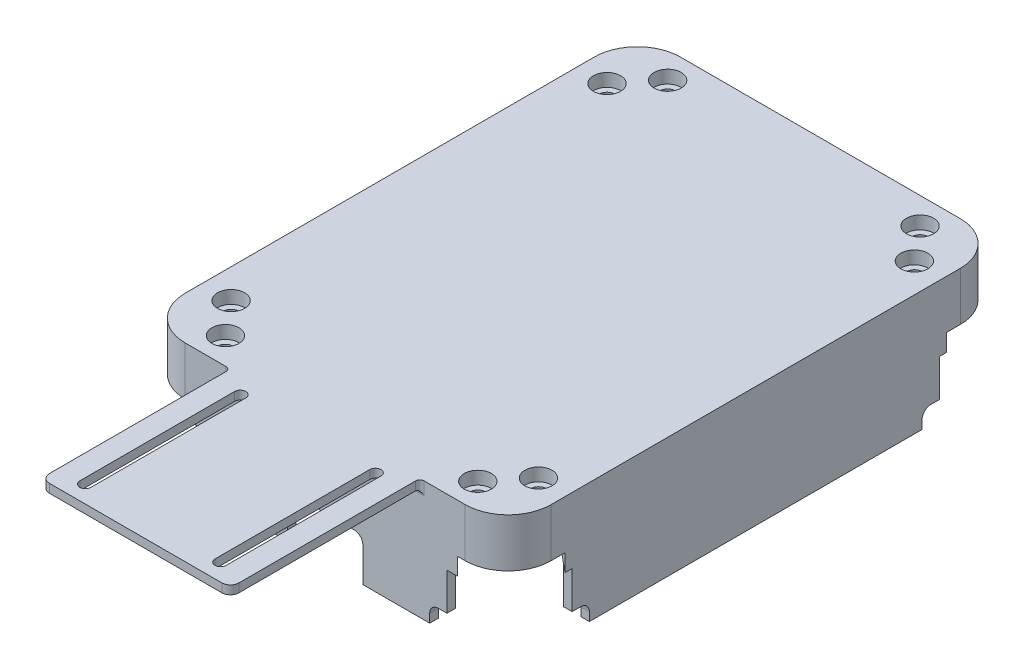
SolidWorks part; units mm, degrees
note: '?' marks a value the reader was unsure of.
material "3-D Printed ABS"
ref_plane "Front Plane" through (0, 0, 0) normal (0, 0, 1) x (1, 0, 0)
ref_plane "Top Plane" through (0, 0, 0) normal (0, 1, 0) x (1, 0, 0)
ref_plane "Right Plane" through (0, 0, 0) normal (1, 0, 0) x (0, 0, -1)
sketch "Sketch1" plane through (0, 0, 0) normal (0, 1, 0) x (1, 0, 0)
  line L1 (-53.975, -73.025) -> (53.975, -73.025)
  line L2 (-53.975, -73.025) -> (-53.975, 73.025)
  line L3 (-53.975, 73.025) -> (53.975, 73.025)
  line L4 (53.975, -73.025) -> (53.975, 73.025)
  line L5 (-53.975, -73.025) -> (53.975, 73.025) construction
  line L6 (-53.975, 73.025) -> (53.975, -73.025) construction
  point P0 (0, 0)
  dimension "D1" = 107.95
  dimension "D2" = 146.05
extrude "Boss-Extrude1" add sketch "Sketch1" against normal blind 2.54
sketch "Sketch13" plane through (0, 0, 0) normal (0, 1, 0) x (1, 0, 0)
  line L0 (0, 155.0212) -> (0, -155.0212) construction
  line L1 (0, 0) -> (-92.0171, 0) construction
  line L2 (53.975, -73.025) -> (53.975, 73.025) construction
  line L3 (53.975, -73.025) -> (28.575, -73.025)
  line L4 (53.975, -73.025) -> (53.975, -47.625)
  line L5 (53.975, -47.625) -> (28.575, -47.625)
  line L6 (28.575, -73.025) -> (28.575, -47.625)
  line L7 (-53.975, -73.025) -> (53.975, -73.025) construction
  line L8 (-28.575, -73.025) -> (-28.575, -47.625)
  line L9 (-53.975, -47.625) -> (-28.575, -47.625)
  line L10 (-53.975, -73.025) -> (-53.975, -47.625)
  line L11 (-53.975, -73.025) -> (-28.575, -73.025)
  line L12 (-53.975, 73.025) -> (-28.575, 73.025)
  line L13 (-53.975, 73.025) -> (-53.975, 47.625)
  line L14 (-53.975, 47.625) -> (-28.575, 47.625)
  line L15 (-28.575, 73.025) -> (-28.575, 47.625)
  line L16 (28.575, 73.025) -> (28.575, 47.625)
  line L17 (53.975, 47.625) -> (28.575, 47.625)
  line L18 (53.975, 73.025) -> (53.975, 47.625)
  line L19 (53.975, 73.025) -> (28.575, 73.025)
  dimension "D1" = 25.4
  dimension "D2" = 25.4
extrude "Boss-Extrude4" add sketch "Sketch13" against normal blind 19.431
sketch "Sketch2" plane through (0, 0, 0) normal (0, 1, 0) x (1, 0, 0)
  line L0 (0, 0) -> (100.1618, 0) construction
  line L1 (0, 0) -> (0, 86.3534) construction
  line L2 (53.975, 73.025) -> (-53.975, 73.025) construction
  line L3 (-53.975, 73.025) -> (-53.975, -73.025) construction
  line L4 (0, 0) -> (-53.975, 73.025) construction
  line L5 (0, 0) -> (-152.4, 0) construction
  line L6 (-152.4, 0) -> (-152.4, 152.4) construction
  line L7 (-152.4, 152.4) -> (0, 152.4) construction
  line L8 (0, 152.4) -> (0, 86.3534) construction
  line L9 (-152.4, 152.4) -> (0, 0) construction
  line L10 (-152.4, 152.4) -> (-41.275, 60.325) construction
  line L11 (-41.275, 60.325) -> (0, 26.1257) construction
  line L13 (-53.975, 44.9974) -> (-30.7521, 73.025) construction
  circle A0 centre (45.3264, 55.4354) radius 3.302
  circle A1 centre (37.2236, 65.2146) radius 3.302
  circle A2 centre (45.3264, -55.4354) radius 3.302
  circle A3 centre (37.2236, -65.2146) radius 3.302
  circle A4 centre (-37.2236, 65.2146) radius 3.302
  circle A5 centre (-45.3264, 55.4354) radius 3.302
  circle A6 centre (-45.3264, -55.4354) radius 3.302
  circle A7 centre (-37.2236, -65.2146) radius 3.302
  point P15 (-41.275, 60.325)
  dimension "D1" = 6.35
  dimension "D3" = 12.7
  dimension "D4" = 6.604
  dimension "D5" = 6.604
  dimension "D2" = 12.7
  dimension "D6" = 6.35
extrude "Cut-Extrude1" cut sketch "Sketch2" against normal through all
sketch "Sketch3" plane through (0, 0, 0) normal (0, 1, 0) x (1, 0, 0)
  line L0 (-53.975, 25.4) -> (53.975, 25.4) construction
  line L1 (-23.495, 60.325) -> (-19.05, 60.325)
  line L2 (-23.495, 60.325) -> (-23.495, 44.45)
  line L3 (-23.495, 44.45) -> (-19.05, 44.45)
  line L4 (-19.05, 60.325) -> (-19.05, 44.45)
  line L5 (19.05, 60.325) -> (19.05, 44.45)
  line L6 (23.495, 44.45) -> (19.05, 44.45)
  line L7 (23.495, 60.325) -> (23.495, 44.45)
  line L8 (23.495, 60.325) -> (19.05, 60.325)
  line L9 (-53.975, 73.025) -> (-53.975, -73.025) construction
  line L10 (53.975, -73.025) -> (53.975, 73.025) construction
  line L11 (0, 0) -> (0, 97.7255) construction
  line L12 (0, 50.8) -> (0, -46.9255) construction
  line L13 (23.495, -9.525) -> (19.05, -9.525)
  line L14 (23.495, -9.525) -> (23.495, 6.35)
  line L15 (23.495, 6.35) -> (19.05, 6.35)
  line L16 (19.05, -9.525) -> (19.05, 6.35)
  line L17 (-19.05, -9.525) -> (-19.05, 6.35)
  line L18 (-23.495, 6.35) -> (-19.05, 6.35)
  line L19 (-23.495, -9.525) -> (-23.495, 6.35)
  line L20 (-23.495, -9.525) -> (-19.05, -9.525)
  dimension "D1" = 15.875
  dimension "D2" = 4.445
  dimension "D3" = 19.05
  dimension "D4" = 25.4
  dimension "D5" = 44.45
extrude "Cut-Extrude2" [suppressed] cut sketch "Sketch3" against normal through all
fillet "Fillet1" radius 12.7 4 edges at (53.975, -9.7155, -73.025) (53.975, -9.7155, 73.025) (-53.975, -9.7155, 73.025) (-53.975, -9.7155, -73.025)
sketch "Sketch4" plane through (0, 0, 0) normal (0, 1, 0) x (1, 0, 0)
  line L0 (0, 0) -> (80.9727, -80.9727) construction
  line L1 (0, 0) -> (-80.9727, -80.9727) construction
  line L2 (69.1118, -51.1513) -> (28.7006, -10.7401)
  line L3 (28.7006, -10.7401) -> (10.7401, -28.7006)
  line L4 (10.7401, -28.7006) -> (51.1513, -69.1118)
  line L5 (51.1513, -69.1118) -> (69.1118, -51.1513)
  line L6 (0, 0) -> (0, -118.7381) construction
  line L7 (0, 0) -> (-98.4177, 0) construction
  line L8 (-51.1513, -69.1118) -> (-69.1118, -51.1513)
  line L9 (-69.1118, -51.1513) -> (-28.7006, -10.7401)
  line L10 (-28.7006, -10.7401) -> (-10.7401, -28.7006)
  line L11 (-10.7401, -28.7006) -> (-51.1513, -69.1118)
  line L12 (-69.1118, 51.1513) -> (-28.7006, 10.7401)
  line L13 (-51.1513, 69.1118) -> (-69.1118, 51.1513)
  line L14 (-10.7401, 28.7006) -> (-51.1513, 69.1118)
  line L15 (-28.7006, 10.7401) -> (-10.7401, 28.7006)
  line L16 (51.1513, 69.1118) -> (69.1118, 51.1513)
  line L17 (69.1118, 51.1513) -> (28.7006, 10.7401)
  line L18 (28.7006, 10.7401) -> (10.7401, 28.7006)
  line L19 (10.7401, 28.7006) -> (51.1513, 69.1118)
  point P6 (19.7204, -19.7204)
  dimension "D1" = 25.4
  dimension "D2" = 57.15
  dimension "D3" = 45
extrude "Cut-Extrude3" [suppressed] cut sketch "Sketch4" against normal blind 1.5875
sketch "Sketch6" [suppressed] plane through (0, 0, 0) normal (0, 1, 0) x (1, 0, 0)
  line L0 (46.3377, -44.1074) -> (34.6634, -32.4331) construction
  line L1 (0, 0) -> (0, -117.7376) construction
  line L2 (0, 0) -> (-151.7285, 0) construction
  line L4 (28.1601, -10.1996) -> (10.1996, -28.1601) construction
  line L5 (50.6107, -68.5712) -> (68.5712, -50.6107) construction
  text T0 "ESC" font "Century Gothic" height in points 22
  dimension "D1" = 45
  dimension "D2" = 20.32
  dimension "D3" = 20.32
extrude "Cut-Extrude5" [suppressed] cut sketch "Sketch6" against normal blind 3.175
sketch "Sketch5" plane through (0, 0, 0) normal (0, 1, 0) x (1, 0, 0)
  line L0 (41.275, 73.025) -> (-41.275, 73.025) construction
  line L1 (14.2875, 15.875) -> (-14.2875, 15.875)
  line L2 (14.2875, 15.875) -> (14.2875, 66.675)
  line L3 (14.2875, 66.675) -> (-14.2875, 66.675)
  line L4 (-14.2875, 15.875) -> (-14.2875, 66.675)
  point P4 (0, 15.875)
  dimension "D1" = 50.8
  dimension "D2" = 28.575
  dimension "D3" = 6.35
extrude "Cut-Extrude4" [suppressed] cut sketch "Sketch5" against normal blind 1.5875
ref_axis "Axis1" through (0, 0.3175, 0) along (0, -1, 0)?
pattern_circular "CirPattern1" [suppressed] count 4 over 360 about axis through (0, 0.3175, 0) along (0, -1, 0)
sketch "Sketch7" plane through (0, 0, 0) normal (0, 1, 0) x (1, 0, 0)
  line L0 (0, 0) -> (0, -54.962) construction
  line L1 (63.4018, -13.3522) -> (38.0018, -13.3522)
  line L2 (63.4018, -13.3522) -> (63.4018, 43.7978)
  line L3 (63.4018, 43.7978) -> (38.0018, 43.7978)
  line L4 (38.0018, -13.3522) -> (38.0018, 43.7978)
  line L5 (-38.0018, -13.3522) -> (-38.0018, 43.7978)
  line L6 (-63.4018, 43.7978) -> (-38.0018, 43.7978)
  line L7 (-63.4018, -13.3522) -> (-63.4018, 43.7978)
  line L8 (-63.4018, -13.3522) -> (-38.0018, -13.3522)
  line L9 (-41.275, -73.025) -> (41.275, -73.025) construction
  line L10 (38.5677, -40.64) -> (-18.5823, -40.64)
  line L11 (38.5677, -40.64) -> (38.5677, -66.04)
  line L12 (38.5677, -66.04) -> (-18.5823, -66.04)
  line L13 (-18.5823, -40.64) -> (-18.5823, -66.04)
  line L14 (38.5677, -40.64) -> (-18.5823, -66.04) construction
  line L15 (38.5677, -66.04) -> (-18.5823, -40.64) construction
  line L16 (19.844, -36.1003) -> (-37.306, -36.1003)
  line L17 (19.844, -36.1003) -> (19.844, -61.5003)
  line L18 (19.844, -61.5003) -> (-37.306, -61.5003)
  line L19 (-37.306, -36.1003) -> (-37.306, -61.5003)
  line L20 (19.844, -36.1003) -> (-37.306, -61.5003) construction
  line L21 (19.844, -61.5003) -> (-37.306, -36.1003) construction
  point P11 (9.9927, -53.34)
  point P18 (-8.731, -48.8003)
  dimension "D1" = 57.15
  dimension "D2" = 25.4
  dimension "D3" = 57.15
  dimension "D4" = 25.4
  dimension "D5" = 6.985
  dimension "D6" = 57.15
  dimension "D7" = 25.4
extrude "Cut-Extrude6" [suppressed] cut sketch "Sketch7" against normal blind 1.27
sketch "Sketch8" plane through (0, 0, 0) normal (0, 1, 0) x (1, 0, 0)
  line L7 (19.05, -31.75) -> (-19.05, -31.75)
  line L8 (19.05, -31.75) -> (19.05, 31.75)
  line L9 (19.05, 31.75) -> (-19.05, 31.75)
  line L10 (-19.05, -31.75) -> (-19.05, 31.75)
  point P0 (0, 0)
  dimension "D1" = 38.1
  dimension "D2" = 31.75
  dimension "D3" = 63.5
extrude "Boss-Extrude3" [suppressed] add sketch "Sketch8" along normal blind 2.54
sketch "Sketch11" plane through (0, 0, 0) normal (0, 1, 0) x (1, 0, 0)
  line L1 (19.05, -9.525) -> (-19.05, -9.525)
  line L2 (19.05, -9.525) -> (19.05, 6.35)
  line L3 (19.05, 6.35) -> (-19.05, 6.35)
  line L4 (-19.05, -9.525) -> (-19.05, 6.35)
extrude "Cut-Extrude9" [suppressed] cut sketch "Sketch11" against normal mid plane 2.54
sketch "Sketch12" [suppressed] plane through (0, 0, 0) normal (0, 1, 0) x (1, 0, 0)
  line L0 (-23.495, -9.525) -> (-19.05, -9.525) construction
  line L1 (12.7, -9.525) -> (-12.7, -9.525)
  line L2 (12.7, -9.525) -> (12.7, 6.35)
  line L3 (12.7, 6.35) -> (-12.7, 6.35)
  line L4 (-12.7, -9.525) -> (-12.7, 6.35)
  line L5 (-19.05, 6.35) -> (-23.495, 6.35) construction
  line L6 (19.05, 52.3875) -> (-19.05, 52.3875) construction
  line L7 (19.05, 60.325) -> (19.05, 44.45) construction
  line L8 (-19.05, 44.45) -> (-19.05, 60.325) construction
  line L9 (-12.7, 114.3) -> (-12.7, 98.425)
  line L10 (12.7, 98.425) -> (-12.7, 98.425)
  line L11 (12.7, 114.3) -> (12.7, 98.425)
  line L12 (12.7, 114.3) -> (-12.7, 114.3)
  point P8 (0, -9.525)
  dimension "D1" = 25.4
extrude "Cut-Extrude12" [suppressed] cut sketch "Sketch12" along normal through all
sketch "Sketch9" plane through (0, 0, 0) normal (0, 1, 0) x (1, 0, 0)
  line L1 (25.1579, -52.4084) -> (-25.6421, -52.4084)
  line L2 (25.1579, -52.4084) -> (25.1579, -1.6084)
  line L3 (25.1579, -1.6084) -> (-25.6421, -1.6084)
  line L4 (-25.6421, -52.4084) -> (-25.6421, -1.6084)
  line L5 (25.1579, -52.4084) -> (-25.6421, -1.6084) construction
  line L6 (25.1579, -1.6084) -> (-25.6421, -52.4084) construction
  point P0 (-0.2421, -27.0084)
  dimension "D1" = 50.8
  dimension "D2" = 50.8
fillet "Fillet2" [suppressed] radius 12.7
sketch "Sketch14" plane through (0, -19.431, 0) normal (0, -1, 0) x (1, 0, 0)
  line L0 (0, 0) -> (0, -152.4) construction
  line L1 (0, 0) -> (152.4, 0) construction
  line L2 (0, 0) -> (152.4, -152.4) construction
  line L3 (152.4, -152.4) -> (41.275, -60.325) construction
  line L4 (41.275, -60.325) -> (27.042, -48.5319) construction
  line L5 (27.042, -48.5319) -> (0, -26.1257) construction
  line L6 (20.692, -28.6742) -> (6.35, -45.9835)
  line L7 (6.35, -45.9835) -> (139.0382, -155.9252)
  line L8 (139.0382, -155.9252) -> (153.3802, -138.6158)
  line L9 (153.3802, -138.6158) -> (20.692, -28.6742)
  line L10 (-20.692, -28.6742) -> (-6.35, -45.9835)
  line L11 (-153.3802, -138.6158) -> (-20.692, -28.6742)
  line L12 (-6.35, -45.9835) -> (-139.0382, -155.9252)
  line L13 (-139.0382, -155.9252) -> (-153.3802, -138.6158)
  line L14 (-153.3802, 138.6158) -> (-20.692, 28.6742)
  line L15 (-139.0382, 155.9252) -> (-153.3802, 138.6158)
  line L16 (-6.35, 45.9835) -> (-139.0382, 155.9252)
  line L17 (-20.692, 28.6742) -> (-6.35, 45.9835)
  line L18 (20.692, 28.6742) -> (6.35, 45.9835)
  line L19 (139.0382, 155.9252) -> (153.3802, 138.6158)
  line L20 (153.3802, 138.6158) -> (20.692, 28.6742)
  line L21 (6.35, 45.9835) -> (139.0382, 155.9252)
  line L22 (41.275, -73.025) -> (-41.275, -73.025) construction
  line L23 (53.975, 60.325) -> (53.975, -60.325) construction
  point P3 (13.521, -37.3288)
  point P6 (41.275, -60.325)
  dimension "D1" = 152.4
  dimension "D2" = 152.4
  dimension "D3" = 6.35
  dimension "D4" = 11.2395
  dimension "D5" = 12.7
  dimension "D6" = 12.7
extrude "Cut-Extrude13" cut sketch "Sketch14" against normal blind 5.08
sketch "Sketch15" plane through (0, 0, 0) normal (0, 1, 0) x (1, 0, 0)
  line L0 (0, 0) -> (72.5178, 0) construction
  line L1 (0, 0) -> (0, 124.598) construction
  circle A0 centre (-45.3264, 55.4354) radius 5.08
  circle A1 centre (45.3264, 55.4354) radius 5.08
  circle A2 centre (37.2236, 65.2146) radius 5.08
  circle A3 centre (45.3264, -55.4354) radius 5.08
  circle A4 centre (37.2236, -65.2146) radius 5.08
  circle A5 centre (-37.2236, -65.2146) radius 5.08
  circle A6 centre (-37.2236, 65.2146) radius 5.08
  circle A7 centre (-45.3264, -55.4354) radius 5.08
extrude "Boss-Extrude5" add sketch "Sketch15" against normal offset from surface (11.811 mm away) 2.54 up to face at (-41.6508, -14.351, -60.7008)
hole_wizard "M4 Clearance Hole1" [suppressed] positions "Sketch18" profile "Sketch16" hole size "M4" standard "ANSI Metric"
sketch "Sketch18" plane through (0, -19.05, 0) normal (0, -1, 0) x (-1, 0, 0)
  point P0 (41.275, 60.325)
  point P3 (41.275, -60.325)
  point P6 (-41.275, -60.325)
  point P9 (-41.275, 60.325)
sketch "Sketch16" plane through (-41.275, -19.05, -60.325) normal (1, 0, 0) x (0, 0, -1)
  line L0 (0, 0) -> (0, 19.05)
  line L1 (0, 19.05) -> (2.25, 19.05)
  line L2 (2.25, 19.05) -> (2.25, 0)
  line L5 (2.25, 0) -> (0, 0)
  line L11 (0, -6.35) -> (0, 107.95) construction
  dimension "Thru Hole Dia." = 4.5
  dimension "Thru Hole Depth" = 19.05
hole_wizard "CBORE for M4 SHCS1" [suppressed] positions "Sketch21" profile "Sketch20" counterbore size "M4" standard "ANSI Metric"
sketch "Sketch21" [suppressed] plane through (0, 0, 0) normal (0, 1, 0) x (1, 0, 0)
  point P0 (41.275, 60.325)
  point P3 (-41.275, 60.325)
  point P6 (-41.275, -60.325)
  point P9 (41.275, -60.325)
sketch "Sketch20" plane through (41.275, 0, -60.325) normal (1, 0, 0) x (0, 0, 1)
  line L0 (0, 0) -> (0, 24.13)
  line L1 (0, 24.13) -> (2.25, 24.13)
  line L3 (2.25, 24.13) -> (2.25, 4)
  line L4 (2.25, 4) -> (4, 4)
  line L5 (4, 4) -> (4, 0)
  line L7 (4, 0) -> (0, 0)
  line L11 (0, -6.35) -> (0, 107.95) construction
  dimension "Thru Hole Dia." = 4.5
  dimension "Thru Hole Depth" = 24.13
  dimension "C'Bore Dia." = 8
  dimension "C'Bore Depth" = 4
sketch "Sketch23" plane through (0, -14.351, 0) normal (0, -1, 0) x (1, 0, 0)
  circle A0 centre (-45.3264, -55.4354) radius 2.25
  circle A1 centre (-37.2236, -65.2146) radius 2.25
  dimension "D1" = 4.5
  dimension "D2" = 4.5
extrude "Cut-Extrude14" cut sketch "Sketch23" against normal through all
sketch "Sketch24" plane through (0, 0, 0) normal (0, 1, 0) x (1, 0, 0)
  circle A0 centre (-45.3264, 55.4354) radius 4
  circle A1 centre (-37.2236, 65.2146) radius 4
  dimension "D1" = 8
  dimension "D2" = 8
extrude "Cut-Extrude15" cut sketch "Sketch24" against normal blind 3.81
mirror "Mirror1" about plane through (0, 0, 0) normal (0, 0, 1) of "Cut-Extrude15", "Cut-Extrude14"
mirror "Mirror2" about plane through (0, 0, 0) normal (1, 0, 0) of "Cut-Extrude15", "Cut-Extrude14", "Mirror1"
fillet "Fillet3" radius 12.7 4 edges at (-28.575, -8.4455, -47.625) (28.575, -8.4455, -47.625) (28.575, -8.4455, 47.625) (-28.575, -8.4455, 47.625)
sketch "Sketch25" plane through (0, 0, 0) normal (0, 1, 0) x (1, 0, 0)
  line L0 (0, 0) -> (0, -33.9706) construction
  line L1 (0, 0) -> (63.8751, 0) construction
  circle A0 centre (30.0609, 0) radius 3.4925
  circle A1 centre (30.0609, -24.9682) radius 3.4925
  circle A2 centre (30.0609, 24.9682) radius 3.4925
  circle A3 centre (-30.0609, 24.9682) radius 3.4925
  circle A4 centre (-30.0609, -24.9682) radius 3.4925
  circle A5 centre (-30.0609, 0) radius 3.4925
  dimension "D1" = 6.985
  dimension "D2" = 6.985
  dimension "D3" = 24.9682
  dimension "D4" = 30.0609
extrude "GimbalMount1" [suppressed] cut sketch "Sketch25" against normal through all
sketch "Sketch26" [suppressed] plane through (0, 0, 0) normal (0, 1, 0) x (1, 0, 0)
  circle A0 centre (30.0609, -24.9682) radius 5.715
  circle A1 centre (30.0609, 0) radius 5.715
  circle A2 centre (30.0609, 24.9682) radius 5.715
  circle A3 centre (-30.0609, -24.9682) radius 5.715
  circle A4 centre (-30.0609, 0) radius 5.715
  circle A5 centre (-30.0609, 24.9682) radius 5.715
  dimension "D1" = 11.43
extrude "GimbalMount2" [suppressed] cut sketch "Sketch26" against normal blind 1.524
fillet "Fillet4" radius 1.016 8 edges at (-45.3264, -14.351, 52.1334) (-37.2236, -14.351, 61.9126) (37.2236, -14.351, 68.5166) (45.3264, -14.351, 58.7374) (-45.3264, -14.351, -52.1334) (-37.2236, -14.351, -61.9126) (37.2236, -14.351, -68.5166) (45.3264, -14.351, -58.7374)
sketch "Sketch27" plane through (0, -2.54, 0) normal (0, -1, 0) x (1, 0, 0)
  line L1 (35.9208, -73.025) -> (-35.9208, -73.025)
  line L2 (35.9208, -73.025) -> (35.9208, -70.485)
  line L3 (35.9208, -70.485) -> (-35.9208, -70.485)
  line L4 (-35.9208, -73.025) -> (-35.9208, -70.485)
  line L6 (0, 0) -> (0, -45.0707) construction
  line L7 (0, 0) -> (-77.1364, 0) construction
  line L8 (-35.9208, 73.025) -> (-35.9208, 70.485)
  line L9 (35.9208, 70.485) -> (-35.9208, 70.485)
  line L10 (35.9208, 73.025) -> (35.9208, 70.485)
  line L11 (35.9208, 73.025) -> (-35.9208, 73.025)
  line L13 (53.975, -54.1469) -> (51.435, -54.1469)
  line L14 (53.975, -54.1469) -> (53.975, 54.1469)
  line L15 (53.975, 54.1469) -> (51.435, 54.1469)
  line L16 (51.435, -54.1469) -> (51.435, 54.1469)
  line L17 (-51.435, -54.1469) -> (-51.435, 54.1469)
  line L18 (-53.975, 54.1469) -> (-51.435, 54.1469)
  line L19 (-53.975, -54.1469) -> (-53.975, 54.1469)
  line L20 (-53.975, -54.1469) -> (-51.435, -54.1469)
  line L22 (28.575, -64.3985) -> (38.9863, -73.025) construction
  line L23 (-38.9863, -73.025) -> (-28.575, -64.3985) construction
  line L24 (28.575, -73.025) -> (-28.575, -73.025) construction
  line L25 (53.975, -56.2515) -> (43.5637, -47.625) construction
  line L26 (53.975, 47.625) -> (53.975, -47.625) construction
  line L27 (43.5637, 47.625) -> (53.975, 56.2515) construction
  dimension "D1" = 2.54
  dimension "D2" = 2.54
extrude "Boss-Extrude6" add sketch "Sketch27" along normal blind 32.9882
sketch "Sketch28" plane through (0, 0, -73.025) normal (0, 0, -1) x (-1, 0, 0)
  line L0 (-41.275, 0) -> (41.275, 0) construction
  line L1 (-17.526, -35.5282) -> (17.526, -35.5282)
  line L2 (-16.891, -27.9082) -> (-16.891, -20.6058)
  line L3 (-14.351, -18.0657) -> (14.351, -18.0657)
  line L4 (16.891, -27.9082) -> (16.891, -20.6058)
  line L5 (35.9208, -35.5282) -> (-35.9208, -35.5282) construction
  line L6 (19.431, -30.4482) -> (27.051, -30.4482)
  line L7 (0, -18.0657) -> (0, 0) construction
  line L8 (17.526, -35.5282) -> (29.591, -35.5282)
  line L9 (29.591, -32.9882) -> (29.591, -35.5282)
  line L11 (-19.431, -30.4482) -> (-27.051, -30.4482)
  line L13 (-17.526, -35.5282) -> (-29.591, -35.5282)
  line L14 (-29.591, -32.9882) -> (-29.591, -35.5282)
  arc A0 (-29.591, -32.9882) -> (-27.051, -30.4482) centre (-27.051, -32.9882) cw
  arc A1 (-19.431, -30.4482) -> (-16.891, -27.9082) centre (-19.431, -27.9082) ccw
  arc A2 (-16.891, -20.6058) -> (-14.351, -18.0657) centre (-14.351, -20.6058) cw
  arc A3 (14.351, -18.0657) -> (16.891, -20.6058) centre (14.351, -20.6058) cw
  arc A4 (16.891, -27.9082) -> (19.431, -30.4482) centre (19.431, -27.9082) ccw
  arc A5 (27.051, -30.4482) -> (29.591, -32.9882) centre (27.051, -32.9882) cw
  point P5 (0, -35.5282)
  point P19 (-29.591, -30.4482)
  point P25 (-16.891, -18.0657)
  point P28 (16.891, -18.0657)
  point P34 (29.591, -30.4482)
  dimension "D7" = 2.54
  dimension "D1" = 17.4625
  dimension "D2" = 33.782
  dimension "D3" = 10.16
  dimension "D4" = 5.08
  dimension "D5" = 10.16
  dimension "D6" = 5.08
extrude "Cut-Extrude16" cut sketch "Sketch28" against normal blind 41.656
sketch "Sketch29" plane through (-53.975, 0, 0) normal (-1, 0, 0) x (0, 0, 1)
  line L0 (0, -35.5282) -> (0, -17.4257) construction
  line L1 (-54.1469, -35.5282) -> (-49.0669, -35.5282)
  line L2 (-54.1469, -35.5282) -> (-54.1469, -30.4482)
  line L3 (-54.1469, -30.4482) -> (-51.6069, -30.4482)
  line L4 (-49.0669, -35.5282) -> (-49.0669, -32.9882)
  line L5 (54.1469, -35.5282) -> (-54.1469, -35.5282) construction
  line L6 (49.0669, -35.5282) -> (49.0669, -32.9882)
  line L7 (54.1469, -30.4482) -> (51.6069, -30.4482)
  line L8 (54.1469, -35.5282) -> (54.1469, -30.4482)
  line L9 (54.1469, -35.5282) -> (49.0669, -35.5282)
  arc A0 (-49.0669, -32.9882) -> (-51.6069, -30.4482) centre (-51.6069, -32.9882) ccw
  arc A1 (49.0669, -32.9882) -> (51.6069, -30.4482) centre (51.6069, -32.9882) cw
  dimension "D1" = 2.54
  dimension "D2" = 5.08
  dimension "D3" = 5.08
extrude "Cut-Extrude17" cut sketch "Sketch29" against normal through all
sketch "Sketch30" plane through (0, 0, 73.025) normal (0, 0, 1) x (1, 0, 0)
  line L0 (0, -35.5282) -> (0, -22.969) construction
  line L1 (-35.9208, -35.5282) -> (-30.8408, -35.5282)
  line L2 (-35.9208, -35.5282) -> (-35.9208, -30.4482)
  line L3 (-35.9208, -30.4482) -> (-33.3808, -30.4482)
  line L4 (-30.8408, -35.5282) -> (-30.8408, -32.9882)
  line L5 (35.9208, -35.5282) -> (-35.9208, -35.5282) construction
  line L6 (30.8408, -35.5282) -> (30.8408, -32.9882)
  line L7 (35.9208, -30.4482) -> (33.3808, -30.4482)
  line L8 (35.9208, -35.5282) -> (35.9208, -30.4482)
  line L9 (35.9208, -35.5282) -> (30.8408, -35.5282)
  arc A0 (-30.8408, -32.9882) -> (-33.3808, -30.4482) centre (-33.3808, -32.9882) ccw
  arc A1 (30.8408, -32.9882) -> (33.3808, -30.4482) centre (33.3808, -32.9882) cw
  dimension "D1" = 2.54
  dimension "D2" = 5.08
  dimension "D3" = 5.08
extrude "Cut-Extrude18" cut sketch "Sketch30" against normal through all
sketch "Sketch31" plane through (0, 0, 73.025) normal (0, 0, 1) x (1, 0, 0)
  line L0 (30.8408, -35.5282) -> (-30.8408, -35.5282) construction
  line L1 (-11.1125, -35.5282) -> (11.1125, -35.5282)
  line L2 (-11.1125, -35.5282) -> (-11.1125, -22.8282)
  line L3 (-11.1125, -22.8282) -> (11.1125, -22.8282)
  line L4 (11.1125, -35.5282) -> (11.1125, -22.8282)
  line L5 (0, -22.8282) -> (0, -15.4197) construction
  line L6 (-41.275, 0) -> (41.275, 0) construction
  point P10 (0, 0)
  dimension "D1" = 12.7
  dimension "D2" = 22.225
extrude "Cut-Extrude19" cut sketch "Sketch31" against normal up to next
fillet "Fillet5" radius 2.54 2 edges at (11.1125, -22.8282, 71.755) (-11.1125, -22.8282, 71.755)
sketch "Sketch33" plane through (0, 0, 0) normal (0, 1, 0) x (1, 0, 0)
  line L0 (0, 0) -> (0, -73.025) construction
  line L1 (-41.275, -73.025) -> (41.275, -73.025) construction
  line L2 (0, -73.025) -> (-41.275, -73.025) construction
  line L3 (0, -73.025) -> (41.275, -73.025) construction
  line L4 (-27.94, -73.025) -> (0, -73.025)
  line L5 (0, -73.025) -> (27.94, -73.025)
  line L6 (0, -73.025) -> (0, -100.965) construction
  line L7 (0, -100.965) -> (0, -128.905) construction
  line L8 (0, -128.905) -> (-27.94, -128.905) construction
  line L9 (-27.94, -128.905) -> (-27.94, -100.965) construction
  line L10 (-27.94, -100.965) -> (-27.94, -73.025) construction
  line L11 (0, -128.905) -> (27.94, -128.905) construction
  line L12 (27.94, -128.905) -> (27.94, -100.965) construction
  line L13 (27.94, -100.965) -> (27.94, -73.025) construction
  line L14 (-27.94, -100.965) -> (27.94, -100.965) construction
  line L15 (27.94, -73.025) -> (27.94, -100.965)
  line L16 (27.94, -100.965) -> (27.94, -126.365)
  line L17 (25.4, -128.905) -> (0, -128.905)
  line L18 (0, -128.905) -> (-25.4, -128.905)
  line L19 (-27.94, -126.365) -> (-27.94, -100.965)
  line L20 (-27.94, -100.965) -> (-27.94, -73.025)
  line L21 (-19.939, -78.1385) -> (-19.939, -123.7915) construction
  line L22 (-18.288, -78.1385) -> (-18.288, -123.7915)
  line L23 (-21.59, -78.1385) -> (-21.59, -123.7915)
  line L24 (19.939, -78.1385) -> (19.939, -123.7915) construction
  line L25 (18.288, -78.1385) -> (18.288, -123.7915)
  line L26 (21.59, -78.1385) -> (21.59, -123.7915)
  arc A0 (-18.288, -78.1385) -> (-21.59, -78.1385) centre (-19.939, -78.1385) ccw
  arc A1 (-21.59, -123.7915) -> (-18.288, -123.7915) centre (-19.939, -123.7915) ccw
  arc A2 (18.288, -78.1385) -> (21.59, -78.1385) centre (19.939, -78.1385) cw
  arc A3 (21.59, -123.7915) -> (18.288, -123.7915) centre (19.939, -123.7915) cw
  arc A4 (27.94, -126.365) -> (25.4, -128.905) centre (25.4, -126.365) cw
  arc A5 (-25.4, -128.905) -> (-27.94, -126.365) centre (-25.4, -126.365) cw
  point P20 (-19.939, -100.965)
  point P26 (19.939, -100.965)
  dimension "D6" = 2.54
  dimension "D1" = 27.94
  dimension "D2" = 27.94
  dimension "D3" = 55.88
  dimension "D4" = 6.35
  dimension "D5" = 3.302
extrude "Boss-Extrude7" add sketch "Sketch33" against normal blind 2.54
fillet "Fillet6" radius 1.27 1 edges at (0, -2.54, 73.025)
fillet "Fillet7" radius 1.27 2 edges at (27.94, -1.905, 73.025) (-27.94, -1.905, 73.025)
equation "\"Plate Thickness\"= \"Plate Thickness@Quad Assemb.sldasm\""
equation "\"D1@Boss-Extrude1\"=\"Plate Thickness\""
equation "\"Plate Dim X\"= \"Plate Dim X@Quad Assemb.sldasm\""
equation "\"Plate Dim Y\"= \"Plate Dim Y@Quad Assemb.sldasm\""
equation "\"D1@Boss-Extrude4\"= \"Component Y@Quad Assemb.sldasm\" - \"ArmBase@Arm V4-1.Part\""
equation "\"D4@Sketch14\" = \"ArmBase@Arm V4-1.Part\" / 2 + .005"
equation "\"Dowell Width\"= \"Dowell Width@Quad Assemb.sldasm\""
equation "\"D1@Sketch2\"=\"Dowell Width\""
equation "\"Dowell Height\"= \"Dowell Height@Quad Assemb.sldasm\""
equation "\"D1@Boss-Extrude5\"=\"Dowell Height\""
equation "\"GimbalMount1\"= if ( \"Gimbal Mount@Quad Assemb.sldasm\" = 1 , \"unsuppressed\" , \"suppressed\" )"
equation "\"GimbalMount2\"= if ( \"Gimbal Mount@Quad Assemb.sldasm\" = 1 , \"unsuppressed\" , \"suppressed\" )"
equation "\"D1@Boss-Extrude6\"=\"Component Y@Quad Assemb.sldasm\"-.31-1/32in"
equation "\"D1@Sketch28\"=\"radio rx Z@Quad Assemb.sldasm\"+3/16"
equation "\"D2@Sketch28\"=\"radio rx x@quad assemb.sldasm\"+.2"
equation "\"D4@Sketch2\"=\"Dowell Width\"+0.01in"
equation "\"D5@Sketch2\"=\"Dowell Width\"+0.01in"
equation "\"D6@Sketch2\"=\"Dowell Width\""
